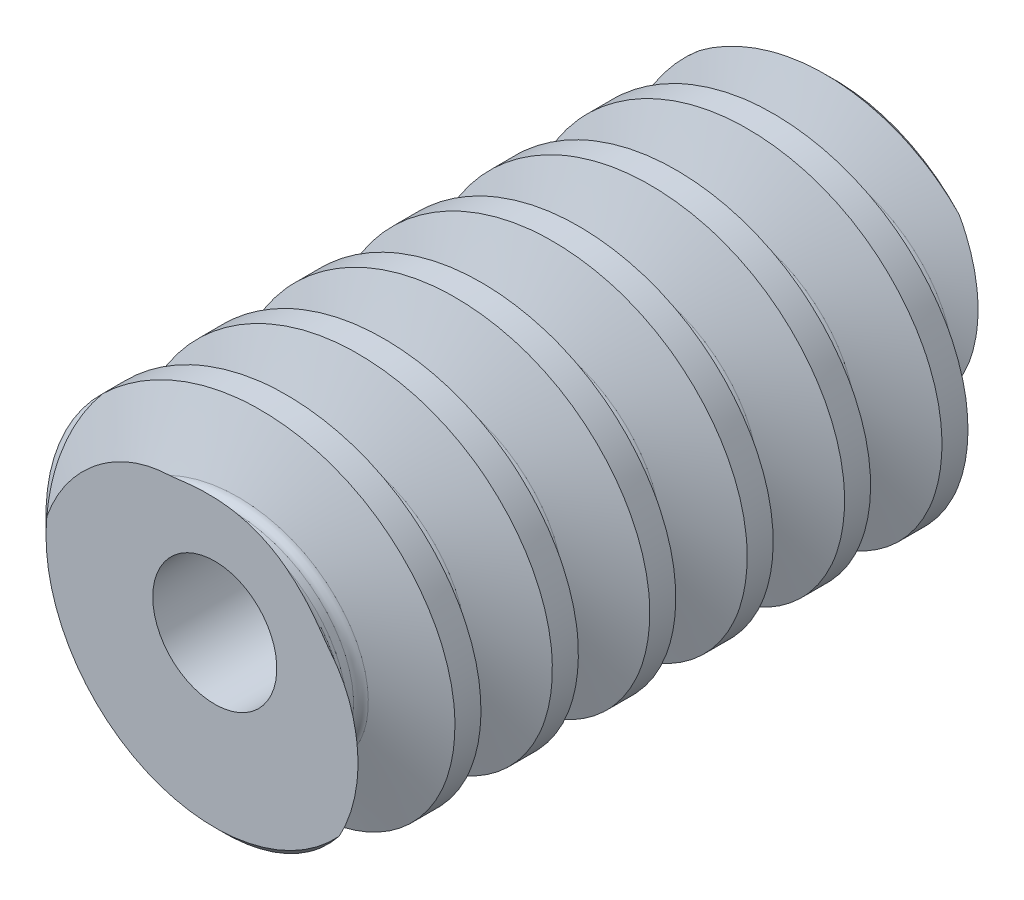
SolidWorks part; units mm, degrees
ref_plane "Front Plane" through (0, 0, 0) normal (0, 0, 1) x (1, 0, 0)
ref_plane "Top Plane" through (0, 0, 0) normal (0, 1, 0) x (1, 0, 0)
ref_plane "Right Plane" through (0, 0, 0) normal (1, 0, 0) x (0, 0, -1)
ref_axis "Axis1" through (0, 0, 55) along (0, 0, -1)
sketch "旋转草图蜗杆01" plane through (0, 0, 0) normal (1, 0, 0) x (0, 0, -1)
  line L0 (0, 0) -> (1, 0) construction
  line L1 (5, 0) -> (5, 2.722)
  line L2 (5, 2.722) -> (4.722, 3)
  line L3 (4.722, 3) -> (-4.722, 3)
  line L4 (-4.722, 3) -> (-5, 2.722)
  line L5 (-5, 2.722) -> (-5, 0)
  line L6 (-5, 0) -> (5, 0)
  dimension "Side1" = 5
  dimension "ChamferX" = 0.278
  dimension "ChamferY" = 0.278
  dimension "OutsideDiameter" = 3
  dimension "WormLength" = 10
revolve "蜗杆01" add sketch "旋转草图蜗杆01" angle 360 about L0
ref_plane "螺旋面蜗杆01" through (0, 0, 6.2832) normal (0, 0, 1) x (1, 0, 0)
sketch "螺旋草图蜗杆01" plane through (0, 0, 6.2832) normal (0, 0, 1) x (1, 0, 0)
  circle A0 centre (0, 0) radius 2.5
  dimension "PitchDiameter" = 5
curve "齿轮螺旋线蜗杆01" pitch 1.5708 height 12.5664 radius 2.5 centre (0, 0, 6.2832) axis (0, 0, -1) start towards (1, 0, 0)
sketch "齿草图蜗杆01" plane through (0, 0, 0) normal (0, 1, 0) x (1, 0, 0)
  line L0 (3.125, -5.6618) -> (1.9735, -6.0832)
  line L1 (1.875, -6.224) -> (1.875, -6.3423)
  line L2 (1.9735, -6.4832) -> (3.125, -6.9046)
  line L3 (3.125, -6.9046) -> (3.125, -5.6618)
  arc A0 (1.9735, -6.0832) -> (1.875, -6.224) centre (2.025, -6.224) ccw
  arc A1 (1.875, -6.3423) -> (1.9735, -6.4832) centre (2.025, -6.3423) ccw
sweep "齿切除蜗杆01" cut profiles "齿草图蜗杆01" path "齿轮螺旋线蜗杆01" align with end faces yes
sketch "孔旋转草图" plane through (0, 0, 0) normal (1, 0, 0) x (0, 0, -1)
  line L0 (-5, 0) -> (5, 0)
  line L1 (5, 0) -> (5, 1)
  line L2 (5, 1) -> (-5, 1)
  line L3 (-5, 1) -> (-5, 0)
  dimension "BoreSide1" = 5
  dimension "TaperSide1" = 1
  dimension "BoreSide2" = 5
  dimension "TaperSide2" = 1
sketch "辅助草图蜗杆01" plane through (0, 0, 0) normal (0, 0, 1) x (1, 0, 0)
  circle A0 centre (0, 0) radius 2.5 construction
  dimension "PitchDiameter" = 5
sketch "Sketch6" plane through (0, 0, -5) normal (0, 0, -1) x (-1, 0, 0)
  circle A0 centre (0, 0) radius 1
  dimension "D1" = 2
extrude "Extrude1" cut sketch "Sketch6" against normal blind 10
